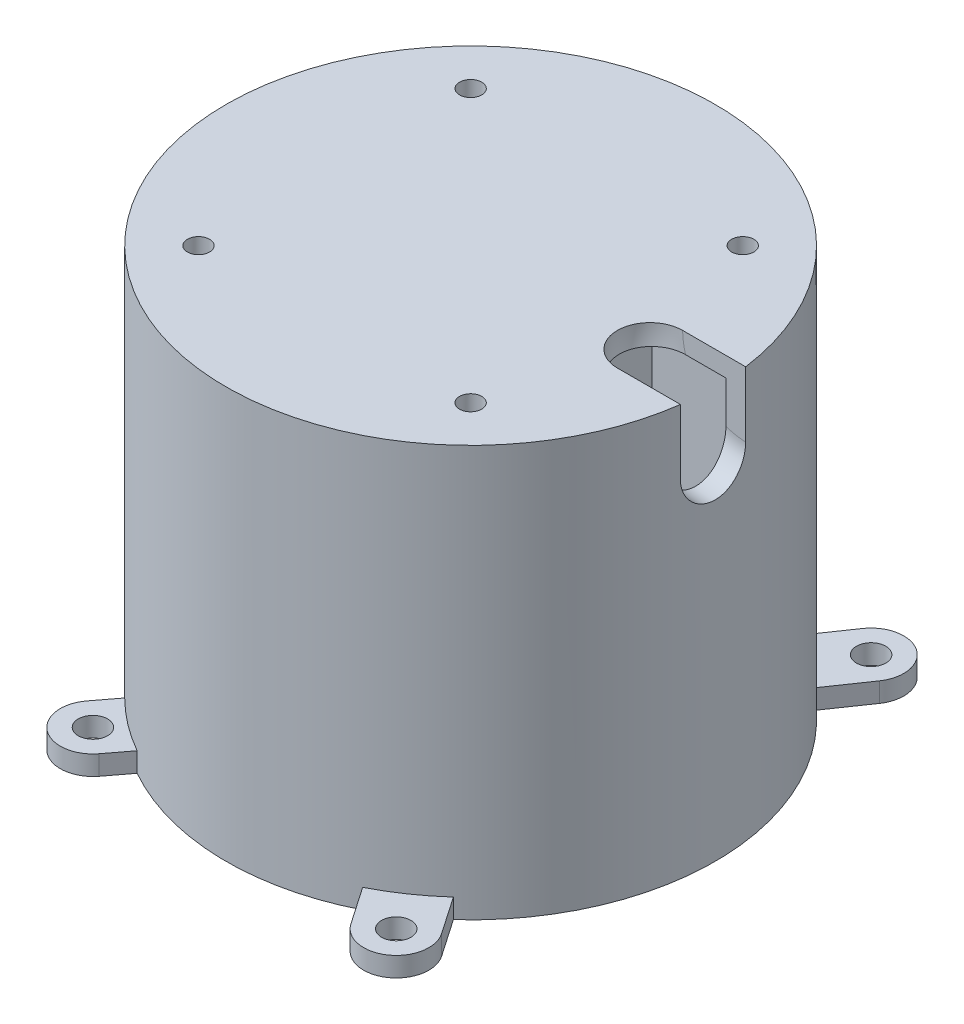
SolidWorks part; units mm, degrees
ref_plane "Front Plane" through (0, 0, 0) normal (0, 0, 1) x (1, 0, 0)
ref_plane "Top Plane" through (0, 0, 0) normal (0, 1, 0) x (1, 0, 0)
ref_plane "Right Plane" through (0, 0, 0) normal (1, 0, 0) x (0, 0, -1)
sketch "Sketch1" plane through (0, 0, 0) normal (0, 1, 0) x (1, 0, 0)
  circle A6 centre (0, 0) radius 37.5
  dimension "D1" = 75
extrude "Boss-Extrude2" add sketch "Sketch1" against normal blind 3
sketch "Sketch2" plane through (0, -3, 0) normal (0, -1, 0) x (1, 0, 0)
  line L4 (0, 32.7824) -> (0, 0) construction
  circle A0 centre (0, 0) radius 34.5
  circle A1 centre (0, 0) radius 37.5
  circle A2 centre (0, 0) radius 37.5
  dimension "D2" = 3
  dimension "D1" = 0
extrude "Boss-Extrude3" add sketch "Sketch2" along normal blind 60
sketch "Sketch3" plane through (0, -3, 0) normal (0, -1, 0) x (1, 0, 0)
  line L0 (13.5, 34.9857) -> (13.5, 31.749)
  line L8 (13.5, 31.749) -> (-13.5, 31.749)
  line L9 (-13.5, 31.749) -> (-13.5, 34.9857)
  line L10 (0, 0) -> (-12.0832, 0) construction
  line L11 (-13.5, -31.749) -> (-13.5, -34.9857)
  line L12 (13.5, -31.749) -> (-13.5, -31.749)
  line L13 (13.5, -34.9857) -> (13.5, -31.749)
  circle A4 centre (0, 0) radius 37.5 construction
  arc A5 (13.5, 34.9857) -> (-13.5, 34.9857) centre (0, 0) ccw
  circle A6 centre (0, 0) radius 34.5 construction
  arc A7 (13.5, -34.9857) -> (-13.5, -34.9857) centre (0, 0) cw
  dimension "D1" = 27
extrude "Boss-Extrude4" add sketch "Sketch3" along normal up to surface (60 mm away) up to face at (0, -63, -37.5)
sketch "Sketch4" plane through (0, 0, 0) normal (0, 0, 1) x (1, 0, 0)
  line L0 (-12.625, -14.83) -> (-12.625, -9.67) construction
  line L1 (12.625, -9.67) -> (12.625, -14.83) construction
  line L2 (-12.625, -14.83) -> (-12.625, -9.67) construction
  line L3 (12.625, -9.67) -> (12.625, -14.83) construction
  line L4 (-12.825, -3) -> (-12.825, -14.83)
  line L5 (-12.125, -17.0499) -> (-12.125, -19.0499)
  line L6 (-12.125, -19.0499) -> (-17.825, -19.0499)
  line L7 (-17.825, -19.0499) -> (-17.825, -3)
  line L8 (-17.825, -3) -> (-12.825, -3)
  line L10 (0, 0) -> (0, -13.0317) construction
  line L11 (17.825, -19.0499) -> (17.825, -3)
  line L12 (12.125, -19.0499) -> (17.825, -19.0499)
  line L13 (12.125, -17.0499) -> (12.125, -19.0499)
  line L14 (12.825, -3) -> (12.825, -14.83)
  line L15 (17.825, -3) -> (12.825, -3)
  line L16 (13.5, -3) -> (34.5, -3) construction
  arc A0 (-12.825, -14.83) -> (-12.125, -17.0499) centre (-8.955, -14.83) ccw
  arc A2 (12.825, -14.83) -> (12.125, -17.0499) centre (8.955, -14.83) cw
  arc A3 (-12.625, -14.83) -> (-8.955, -18.5) centre (-8.955, -14.83) ccw construction
  dimension "D1" = 0.2
  dimension "D2" = 0.7
  dimension "D3" = 2
  dimension "D4" = 5
extrude "Boss-Extrude5" add sketch "Sketch4" along normal mid plane 20
ref_plane "Plane1" through (37.5, 0, 0) normal (1, 0, 0) x (0, 0, -1)
sketch "Sketch7" plane through (0, -63, 0) normal (0, -1, 0) x (1, 0, 0)
  circle A0 centre (0, 0) radius 37.5
  circle A1 centre (0, 0) radius 31.5
  circle A2 centre (0, 0) radius 37.5 construction
  dimension "D1" = 6
extrude "Boss-Extrude7" add sketch "Sketch7" against normal blind 3
hole_wizard "M3 Clearance Hole1" positions "Sketch8" profile "Sketch10" hole size "M3" standard "ANSI Metric" end condition through all
sketch "Sketch8" plane through (0, -3, 0) normal (0, -1, 0) x (-1, 0, 0)
  circle A2 centre (20.8597, -20.8597) radius 1.6
  circle A3 centre (20.8597, -20.8597) radius 1.6
  circle A6 centre (-20.8597, -20.8597) radius 1.6
  circle A7 centre (-20.8597, -20.8597) radius 1.6
  circle A10 centre (-20.8597, 20.8597) radius 1.6
  circle A11 centre (-20.8597, 20.8597) radius 1.6
  circle A14 centre (20.8597, 20.8597) radius 1.6
  circle A15 centre (20.8597, 20.8597) radius 1.6
  point P5 (20.8597, -20.8597)
  point P12 (-20.8597, -20.8597)
  point P19 (-20.8597, 20.8597)
  point P26 (20.8597, 20.8597)
  dimension "D1" = 0
  dimension "D2" = 0
  dimension "D3" = 0
  dimension "D4" = 0
sketch "Sketch10" plane through (-20.8597, -3, 20.8597) normal (1, 0, 0) x (0, 0, -1)
  line L0 (0, 0) -> (0, 3)
  line L1 (0, 3) -> (1.7, 3)
  line L2 (1.7, 3) -> (1.7, 0)
  line L5 (1.7, 0) -> (0, 0)
  line L11 (0, -6.35) -> (0, 107.95) construction
  dimension "Thru Hole Dia." = 3.4
  dimension "Thru Hole Depth" = 3
sketch "Sketch11" plane through (0, 0, 0) normal (0, 1, 0) x (1, 0, 0)
  line L0 (37.5, -5) -> (27.5, -5)
  line L1 (27.5, 5) -> (37.5, 5)
  line L2 (27.5, 0) -> (0, 0) construction
  line L3 (37.5, -5) -> (37.5, 5)
  arc A0 (27.5, -5) -> (27.5, 5) centre (27.5, 0) cw
  circle A1 centre (0, 0) radius 37.5 construction
  point P2 (22.5, 0)
  point P4 (37.5, 0)
  dimension "D3" = 15
  dimension "D2" = 10
revolve "Cut-Revolve1" cut sketch "Sketch11" angle 360 about L3
sketch "Sketch14" plane through (0, -63, 0) normal (0, -1, 0) x (1, 0, 0)
  line L0 (25, 36.4) -> (25, 32.9)
  line L1 (25, 32.9) -> (-25, 32.9)
  line L2 (0, -32.9) -> (0, 32.9)
  line L3 (0, 0) -> (13.3551, 0) construction
  line L4 (25, -32.9) -> (-25, -32.9)
  line L5 (25, -36.4) -> (25, -32.9)
  point P6 (0, 0)
  point P7 (0, 0)
  dimension "D1" = 3.5
  dimension "D2" = 50
  dimension "D3" = 65.8
sketch "Sketch15" plane through (0, -63, 0) normal (0, -1, 0) x (1, 0, 0)
  line L0 (25.1624, 27.8048) -> (29.1215, 33.5693)
  line L1 (20.8785, 39.2307) -> (16.9193, 33.4662)
  line L2 (-26.4668, 26.5661) -> (-28.981, 29.8749)
  line L3 (-21.019, 35.9251) -> (-18.5047, 32.6163)
  line L5 (-25, 32.9) -> (0, 0) construction
  line L6 (0, 0) -> (25, 36.4) construction
  line L7 (0, 0) -> (-26.4668, 0) construction
  line L8 (-21.019, -35.9251) -> (-18.5047, -32.6163)
  line L9 (-26.4668, -26.5661) -> (-28.981, -29.8749)
  line L10 (25.1624, -27.8048) -> (29.1215, -33.5693)
  line L11 (20.8785, -39.2307) -> (16.9193, -33.4662)
  circle A0 centre (0, 0) radius 37.5 construction
  arc A1 (29.1215, 33.5693) -> (20.8785, 39.2307) centre (25, 36.4) ccw
  arc A2 (-18.5047, 32.6163) -> (-26.4668, 26.5661) centre (0, 0) ccw
  arc A3 (-28.981, 29.8749) -> (-21.019, 35.9251) centre (-25, 32.9) cw
  arc A4 (25.1624, 27.8048) -> (16.9193, 33.4662) centre (0, 0) ccw
  arc A5 (-28.981, -29.8749) -> (-21.019, -35.9251) centre (-25, -32.9) ccw
  arc A6 (-18.5047, -32.6163) -> (-26.4668, -26.5661) centre (0, 0) cw
  arc A7 (29.1215, -33.5693) -> (20.8785, -39.2307) centre (25, -36.4) cw
  arc A8 (25.1624, -27.8048) -> (16.9193, -33.4662) centre (0, 0) cw
  dimension "D1" = 10
extrude "Boss-Extrude8" add sketch "Sketch15" against normal blind 3
hole_wizard "#8 Clearance Hole1" positions "Sketch16" profile "Sketch17" hole size "#8" standard "ANSI Inch" end condition through all
sketch "Sketch16" plane through (0, -63, 0) normal (0, -1, 0) x (-1, 0, 0)
  point P0 (-25, -36.4)
  point P3 (25, -32.9)
  point P6 (-25, 36.4)
  point P9 (25, 32.9)
sketch "Sketch17" plane through (25, -63, 36.4) normal (1, 0, 0) x (0, 0, -1)
  line L0 (0, 0) -> (0, 63)
  line L1 (0, 63) -> (2.2479, 63)
  line L2 (2.2479, 63) -> (2.2479, 0)
  line L5 (2.2479, 0) -> (0, 0)
  line L11 (0, -6.35) -> (0, 107.95) construction
  dimension "Thru Hole Dia." = 4.4958
  dimension "Thru Hole Depth" = 63
sketch "Sketch18" plane through (0, -3, 0) normal (0, -1, 0) x (1, 0, 0)
  line L1 (-12.825, 20) -> (12.825, 20)
  line L2 (-12.825, 20) -> (-12.825, -20)
  line L3 (-12.825, -20) -> (12.825, -20)
  line L4 (12.825, 20) -> (12.825, -20)
  line L5 (-12.825, 20) -> (12.825, -20) construction
  line L6 (-12.825, -20) -> (12.825, 20) construction
  point P0 (0, 0)
  dimension "D1" = 40
extrude "Boss-Extrude9" add sketch "Sketch18" along normal blind 3
sketch "Sketch19" plane through (0, 0, -31.749) normal (0, 0, 1) x (1, 0, 0)
  line L0 (8.955, -18.5) -> (-8.955, -18.5) construction
  line L1 (10.75, -5.5) -> (-10.75, -5.5)
  line L2 (10.75, -5.5) -> (10.75, -18.5)
  line L3 (10.75, -18.5) -> (-10.75, -18.5)
  line L4 (-10.75, -5.5) -> (-10.75, -18.5)
  line L5 (0, 0) -> (0, -5.5) construction
  line L6 (-8.955, -6) -> (5.61, -6) construction
  line L7 (-8.955, -6) -> (5.61, -6) construction
  dimension "D1" = 1
  dimension "D2" = 21.5
extrude "Cut-Extrude4" cut sketch "Sketch19" against normal through all
fillet "Fillet2" radius 2 4 edges at (-10.75, -5.5, -33.8376) (10.75, -5.5, -33.8376) (10.75, -18.5, -33.8376) (-10.75, -18.5, -33.8376)
